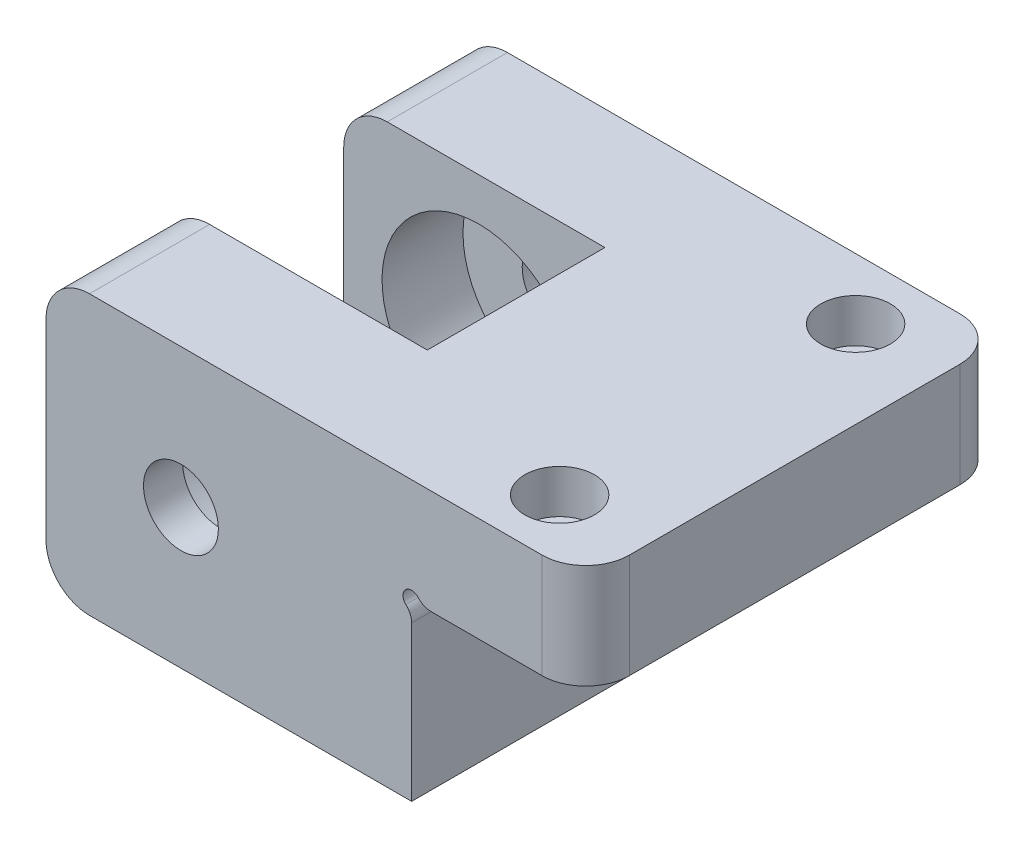
SolidWorks part; units mm, degrees
material "ABS"
ref_plane "Płaszczyzna przednia" through (0, 0, 0) normal (0, 0, 1) x (1, 0, 0)
ref_plane "Płaszczyzna górna" through (0, 0, 0) normal (0, 1, 0) x (1, 0, 0)
ref_plane "Płaszczyzna prawa" through (0, 0, 0) normal (1, 0, 0) x (0, 0, -1)
sketch "Szkic1" plane through (0, 0, 0) normal (0, 0, 1) x (1, 0, 0)
  line L0 (0, 0) -> (0, 17.7639)
  line L1 (2.2361, 20) -> (20, 20)
  line L2 (20, 20) -> (20, 32)
  line L3 (20, 32) -> (-12, 32)
  line L4 (-12, 32) -> (-12, 0)
  line L5 (-12, 0) -> (0, 0)
  arc A0 (0.7454, 20.6667) -> (-0.6667, 19.2546) centre (0, 20) ccw
  arc A1 (2.2361, 20) -> (0.7454, 20.6667) centre (2.2361, 22) cw
  arc A2 (0, 17.7639) -> (-0.6667, 19.2546) centre (-2, 17.7639) ccw
  dimension "D5" = 2
  dimension "D6" = 2
  dimension "D1" = 20
  dimension "D2" = 20
  dimension "D3" = 12
  dimension "D4" = 12
  dimension "D7" = 20
  dimension "D8" = 20
extrude "Dodanie-wyciągnięcie1" add sketch "Szkic1" along normal blind 48 contours L0 A2 A0 A1 L1 L2 L3 L4 L5
sketch "Szkic4" plane through (-12, 0, 0) normal (-1, 0, 0) x (0, 0, 1)
  line L0 (48, 32) -> (0, 32) construction
  line L1 (48, 0) -> (34.2, 0)
  line L2 (48, 0) -> (48, 32)
  line L3 (48, 32) -> (34.2, 32)
  line L4 (34.2, 0) -> (34.2, 32)
  line L5 (48, 0) -> (0, 0) construction
  line L6 (0, 32) -> (13.8, 32)
  line L7 (0, 32) -> (0, 0)
  line L8 (0, 0) -> (13.8, 0)
  line L9 (13.8, 32) -> (13.8, 0)
  dimension "D1" = 13.8
  dimension "D2" = 13.8
extrude "Dodanie-wyciągnięcie3" add sketch "Szkic4" along normal blind 30
sketch "Szkic6" plane through (0, 0, 48) normal (0, 0, 1) x (1, 0, 0)
  line L4 (-12, 0) -> (-12, 32)
  line L5 (-12, 32) -> (-42, 32)
  line L6 (-42, 32) -> (-42, 0)
  line L7 (-42, 0) -> (-12, 0)
  line L8 (-12, 0) -> (-12, 32)
  line L9 (-12, 32) -> (-42, 32)
  line L10 (-42, 32) -> (-42, 0)
  line L11 (-42, 0) -> (-12, 0)
  circle A0 centre (-26.5, 16) radius 11.1
  dimension "D2" = 22.2
  dimension "D4" = 14.5
  dimension "D3" = 16
  dimension "D1" = 0
extrude "Wytnij-wyciągnięcie1" cut sketch "Szkic6" against normal through all contours A0 region at (-26.5, 16, 48)
sketch "Szkic9" plane through (0, 32, 0) normal (0, 1, 0) x (1, 0, 0)
  line L4 (20, 0) -> (2.2361, 0)
  line L5 (20, -48) -> (20, 0)
  line L6 (2.2361, -48) -> (20, -48)
  line L7 (2.2361, 0) -> (2.2361, -48)
  line L8 (20, 0) -> (2.2361, 0)
  line L9 (20, -48) -> (20, 0)
  line L10 (2.2361, -48) -> (20, -48)
  line L11 (2.2361, 0) -> (2.2361, -48)
  circle A0 centre (10, -7) radius 4
  circle A1 centre (10, -41) radius 4
  dimension "D3" = 8
  dimension "D2" = 10
  dimension "D4" = 7
  dimension "D5" = 7
  dimension "D1" = 0
extrude "Wytnij-wyciągnięcie4" cut sketch "Szkic9" against normal blind 5 contours A1 | A0 region at (10, 32, 7) region at (10, 32, 41)
sketch "Szkic10" plane through (0, 27, 0) normal (0, 1, 0) x (1, 0, 0)
  circle A0 centre (10, -7) radius 4 construction
  circle A1 centre (10, -41) radius 4 construction
  circle A2 centre (10, -7) radius 4
  circle A3 centre (10, -41) radius 4
  circle A4 centre (10, -7) radius 2.1
  circle A5 centre (10, -41) radius 2.1
  dimension "D1" = 4.2
extrude "Wytnij-wyciągnięcie5" cut sketch "Szkic10" against normal blind 5 contours A5 | A4 region at (10, 27, 7) region at (10, 27, 41)
fillet "Zaokrąglenie1" radius 5 2 edges at (20, 26, 0) (20, 26, 48)
fillet "Zaokrąglenie2" radius 5 4 edges at (-42, 0, 6.9) (-42, 0, 41.1) (-42, 32, 41.1) (-42, 32, 6.9)
sketch "Szkic11" plane through (0, 0, 48) normal (0, 0, 1) x (1, 0, 0)
  circle A0 centre (-26.5, 16) radius 11.1 construction
  circle A1 centre (-26.5, 16) radius 11.1
extrude "Dodanie-wyciągnięcie5" add sketch "Szkic11" against normal blind 4.5
ref_plane "Płaszczyzna1" through (0, 0, 24) normal (0, 0, 1) x (1, 0, 0)
mirror "Lustro1" about plane through (0, 0, 24) normal (0, 0, 1) of "Dodanie-wyciągnięcie5"
sketch "Szkic12" plane through (0, 0, 48) normal (0, 0, 1) x (1, 0, 0)
  circle A0 centre (-26.5, 16) radius 11.1 construction
  circle A1 centre (-26.5, 16) radius 11.1 construction
  circle A2 centre (-26.5, 16) radius 4.3
  dimension "D1" = 8.6
extrude "Wytnij-wyciągnięcie6" cut sketch "Szkic12" against normal through all
